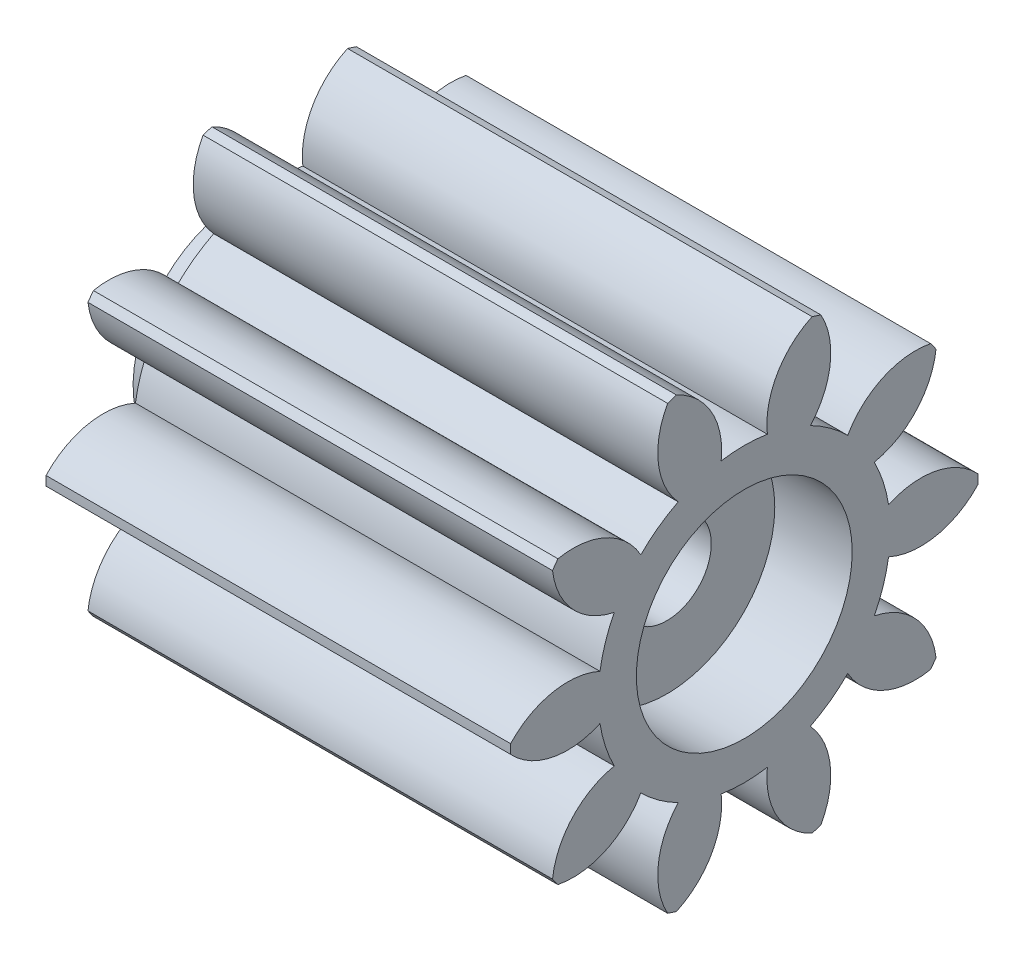
SolidWorks part; units mm, degrees
ref_plane "Front Plane" through (0, 0, 0) normal (0, 0, 1) x (1, 0, 0)
ref_plane "Top Plane" through (0, 0, 0) normal (0, 1, 0) x (1, 0, 0)
ref_plane "Right Plane" through (0, 0, 0) normal (1, 0, 0) x (0, 0, -1)
sketch "Sketch1" plane through (0, 0, 0) normal (1, 0, 0) x (0, 0, -1)
  circle A0 centre (0, 0) radius 1.4
  arc A1 (7.3616, 0.1459) -> (4.5452, 0.712) centre (5.5612, -1.5222) ccw
  arc A2 (4.5452, 0.712) -> (4.0957, 2.0956) centre (0, 0) ccw
  arc A3 (4.0957, 2.0956) -> (6.0414, 4.209) centre (3.6044, 4.5003) ccw
  arc A4 (6.0414, 4.209) -> (5.8699, 4.4451) centre (0, 0) ccw
  arc A5 (5.8699, 4.4451) -> (3.2587, 3.2476) centre (5.3939, 2.0373) ccw
  arc A6 (3.2587, 3.2476) -> (2.0817, 4.1028) centre (0, 0) ccw
  arc A7 (2.0817, 4.1028) -> (2.4136, 6.9562) centre (0.2708, 5.7595) ccw
  arc A8 (2.4136, 6.9562) -> (2.1361, 7.0464) centre (0, 0) ccw
  arc A9 (2.1361, 7.0464) -> (0.7274, 4.5428) centre (3.1662, 4.8187) ccw
  arc A10 (0.7274, 4.5428) -> (-0.7274, 4.5428) centre (0, 0) ccw
  arc A11 (-0.7274, 4.5428) -> (-2.1361, 7.0464) centre (-3.1662, 4.8187) ccw
  arc A12 (-2.1361, 7.0464) -> (-2.4136, 6.9562) centre (0, 0) ccw
  arc A13 (-2.4136, 6.9562) -> (-2.0817, 4.1028) centre (-0.2708, 5.7595) ccw
  arc A14 (-2.0817, 4.1028) -> (-3.2587, 3.2476) centre (0, 0) ccw
  arc A15 (-3.2587, 3.2476) -> (-5.8699, 4.4451) centre (-5.3939, 2.0373) ccw
  arc A16 (-5.8699, 4.4451) -> (-6.0414, 4.209) centre (0, 0) ccw
  arc A17 (-6.0414, 4.209) -> (-4.0957, 2.0956) centre (-3.6044, 4.5003) ccw
  arc A18 (-4.0957, 2.0956) -> (-4.5452, 0.712) centre (0, 0) ccw
  arc A19 (-4.5452, 0.712) -> (-7.3616, 0.1459) centre (-5.5612, -1.5222) ccw
  arc A20 (-7.3616, 0.1459) -> (-7.3616, -0.1459) centre (0, 0) ccw
  arc A21 (-7.3616, -0.1459) -> (-4.5452, -0.712) centre (-5.5612, 1.5222) ccw
  arc A22 (-4.5452, -0.712) -> (-4.0957, -2.0956) centre (0, 0) ccw
  arc A23 (-4.0957, -2.0956) -> (-6.0414, -4.209) centre (-3.6044, -4.5003) ccw
  arc A24 (-6.0414, -4.209) -> (-5.8699, -4.4451) centre (0, 0) ccw
  arc A25 (-5.8699, -4.4451) -> (-3.2587, -3.2476) centre (-5.3939, -2.0373) ccw
  arc A26 (-3.2587, -3.2476) -> (-2.0817, -4.1028) centre (0, 0) ccw
  arc A27 (-2.0817, -4.1028) -> (-2.4136, -6.9562) centre (-0.2708, -5.7595) ccw
  arc A28 (-2.4136, -6.9562) -> (-2.1361, -7.0464) centre (0, 0) ccw
  arc A29 (-2.1361, -7.0464) -> (-0.7274, -4.5428) centre (-3.1662, -4.8187) ccw
  arc A30 (-0.7274, -4.5428) -> (0.7274, -4.5428) centre (0, 0) ccw
  arc A31 (0.7274, -4.5428) -> (2.1361, -7.0464) centre (3.1662, -4.8187) ccw
  arc A32 (2.1361, -7.0464) -> (2.4136, -6.9562) centre (0, 0) ccw
  arc A33 (2.4136, -6.9562) -> (2.0817, -4.1028) centre (0.2708, -5.7595) ccw
  arc A34 (2.0817, -4.1028) -> (3.2587, -3.2476) centre (0, 0) ccw
  arc A35 (3.2587, -3.2476) -> (5.8699, -4.4451) centre (5.3939, -2.0373) ccw
  arc A36 (5.8699, -4.4451) -> (6.0414, -4.209) centre (0, 0) ccw
  arc A37 (6.0414, -4.209) -> (4.0957, -2.0956) centre (3.6044, -4.5003) ccw
  arc A38 (4.0957, -2.0956) -> (4.5452, -0.712) centre (0, 0) ccw
  arc A39 (4.5452, -0.712) -> (7.3616, -0.1459) centre (5.5612, 1.5222) ccw
  arc A40 (7.3616, -0.1459) -> (7.3616, 0.1459) centre (0, 0) ccw
  circle A41 centre (0, 0) radius 3.4
  dimension "D1" = 2.8
  dimension "D2" = 2
extrude "Boss-Extrude1" add sketch "Sketch1" against normal mid plane 12 contours A39 A40 A1 A2 A3 A4 A5 A6 A7 A8 A9 A10 A11 A12 A13 A14 A15 A16 A17 A18 A19 A20 A21 A22 A23 A24 A25 A26 A27 A28 A29 A30 A31 A32 A33 A34 A35 A36 A37 A38 A41 region at (0, 0, -7.1592)
extrude "Boss-Extrude2" add sketch "Sketch1<4>" along normal offset from surface 2 and the other way blind 7 contours A41 A0 region at (0, 0, 3.3038) up to face at (6, 0, -3.4)
sketch "Sketch1<4>" plane through (0, 0, 0) normal (1, 0, 0) x (0, 0, -1) same geometry as "Sketch1"
scale "Scale1" scale about centroid uniform scaling no x scale factor 1 y scale factor 0.82 z scale factor 0.82
